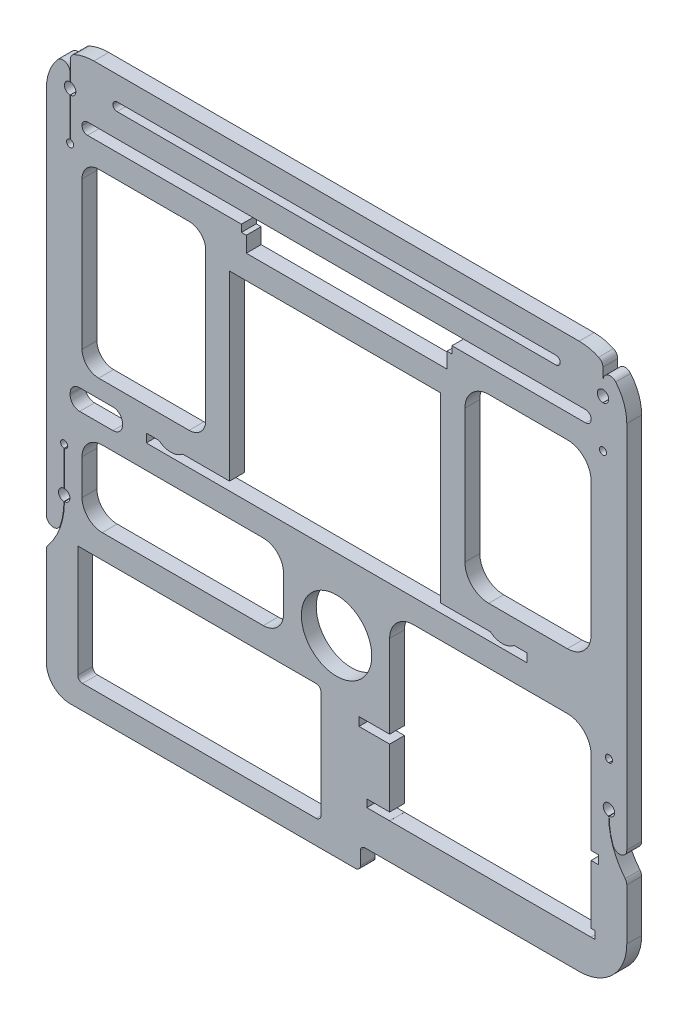
SolidWorks part; units mm, degrees
ref_plane "Front Plane" through (0, 0, 0) normal (0, 0, 1) x (1, 0, 0)
ref_plane "Top Plane" through (0, 0, 0) normal (0, 1, 0) x (1, 0, 0)
ref_plane "Right Plane" through (0, 0, 0) normal (1, 0, 0) x (0, 0, -1)
sketch "Sketch1" plane through (0, 0, 0) normal (0, 0, 1) x (1, 0, 0)
  line L0 (63.9883, 61.406) -> (63.9883, 57.596) construction
  line L1 (11.1776, 3.1158) -> (73.1542, 3.1158)
  line L2 (11.1776, 3.1158) -> (11.1776, 61.406)
  line L3 (11.1776, 61.406) -> (73.1542, 61.406)
  line L4 (73.1542, 3.1158) -> (73.1542, 61.406)
  line L5 (69.3442, 57.596) -> (14.9876, 57.596)
  line L6 (69.3442, 57.596) -> (69.3442, 6.9258)
  line L7 (69.3442, 6.9258) -> (14.9876, 6.9258)
  line L8 (14.9876, 57.596) -> (14.9876, 6.9258)
  line L9 (63.9883, 59.501) -> (18.0707, 59.501) construction
  line L10 (14.9876, 39.3805) -> (11.1776, 39.3805) construction
  line L11 (13.0826, 39.3805) -> (13.0826, 23.9527) construction
  line L12 (13.5248, 6.9258) -> (13.5248, 3.1158) construction
  line L13 (13.5248, 5.0208) -> (21.1598, 5.0208) construction
  line L14 (73.1542, 38.1916) -> (69.3442, 38.1916) construction
  line L15 (71.2492, 38.1916) -> (71.2492, 22.3321) construction
  line L16 (55.7422, 59.501) -> (30.5962, 59.501) construction
  line L19 (42.3087, 5.0208) -> (41.7626, 5.0208) construction
  line L21 (69.3442, 27.6227) -> (69.3442, 52.516) construction
  line L22 (14.9876, 47.563) -> (14.9876, 27.6227) construction
  dimension "D1" = 3.81
  dimension "D2" = 3.81
extrude "Boss-Extrude1" add sketch "Sketch1" along normal blind 1.5875
sketch "Sketch2" plane through (0, 0, 0) normal (0, 0, -1) x (-1, 0, 0)
  line L0 (-69.3442, 6.9258) -> (-69.3442, 57.596) construction
  line L1 (-69.3442, 28.8799) -> (-14.9876, 28.8799)
  line L2 (-69.3442, 28.8799) -> (-69.3442, 26.3399)
  line L3 (-69.3442, 26.3399) -> (-14.9876, 26.3399)
  line L4 (-14.9876, 28.8799) -> (-14.9876, 26.3399)
  line L5 (-14.9876, 57.596) -> (-14.9876, 6.9258) construction
  line L7 (-53.9642, 53.4304) -> (-53.9642, 51.7667)
  line L8 (-32.5266, 53.4304) -> (-32.0059, 53.4304)
  line L9 (-32.5266, 51.7667) -> (-53.9642, 51.7667) construction
  line L10 (-32.5266, 51.7667) -> (-32.5266, 53.4304) construction
  line L11 (-69.3442, 54.1924) -> (-54.4849, 54.1924)
  line L12 (-69.3442, 54.1924) -> (-69.3442, 51.6524)
  line L13 (-69.3442, 51.6524) -> (-55.8692, 51.6524)
  line L14 (-14.9876, 54.1924) -> (-14.9876, 51.6524)
  line L15 (-69.3442, 57.596) -> (-14.9876, 57.596)
  line L16 (-69.3442, 57.596) -> (-69.3442, 55.4243)
  line L17 (-69.3442, 55.4243) -> (-14.9876, 55.4243)
  line L18 (-14.9876, 57.596) -> (-14.9876, 55.4243)
  line L19 (-69.3442, 57.596) -> (-14.9876, 57.596) construction
  line L20 (-54.4849, 54.1924) -> (-54.4849, 53.4304)
  line L21 (-62.3462, 55.4243) -> (-23.9922, 55.4243) construction
  line L22 (-54.4849, 53.4304) -> (-53.9642, 53.4304)
  line L23 (-32.5266, 51.7667) -> (-53.9642, 51.7667)
  line L24 (-32.5266, 51.7667) -> (-32.5266, 53.4304)
  line L25 (-55.8692, 51.6524) -> (-55.8692, 49.2267)
  line L26 (-55.8692, 49.2267) -> (-30.6216, 49.2267)
  line L27 (-30.6216, 49.2267) -> (-30.6216, 51.6524)
  line L28 (-30.6216, 51.6524) -> (-14.9876, 51.6524)
  line L29 (-32.0059, 53.4304) -> (-32.0059, 54.1924)
  line L30 (-62.3462, 54.1924) -> (-23.9922, 54.1924) construction
  line L31 (-62.4859, 28.8799) -> (-21.8459, 28.8799) construction
  line L32 (-54.4849, 53.4304) -> (-54.4849, 54.1924) construction
  line L33 (-32.0059, 53.4304) -> (-54.4849, 53.4304) construction
  line L34 (-32.0059, 54.1924) -> (-14.9876, 54.1924)
  line L36 (-32.0059, 53.4304) -> (-32.0059, 54.1924) construction
  line L37 (-32.5266, 51.7667) -> (-32.5266, 53.4304) construction
  dimension "D1" = 2.54
  dimension "D2" = 1.905
  dimension "D3" = 2.54
  dimension "D4" = 1.905
  dimension "D5" = 2.54
extrude "Boss-Extrude2" add sketch "Sketch2" against normal up to surface (1.5875 mm away) up to face at (42.1659, 32.2609, 1.5875)
sketch "Sketch3" plane through (0, 0, 0) normal (0, 0, -1) x (-1, 0, 0)
  line L1 (-51.983, 32.3343) -> (-51.983, 29.7943) construction
  line L2 (-53.253, 29.7943) -> (-69.3442, 29.7943)
  line L3 (-69.3442, 28.8799) -> (-69.3442, 51.6524) construction
  line L4 (-69.3442, 29.7943) -> (-69.3442, 32.3343)
  line L5 (-69.3442, 32.3343) -> (-55.8692, 32.3343)
  line L7 (-53.253, 29.7943) -> (-53.253, 49.2267)
  line L8 (-55.8692, 49.2267) -> (-30.6216, 49.2267) construction
  line L9 (-53.253, 49.2267) -> (-55.8692, 49.2267)
  line L10 (-55.8692, 49.2267) -> (-55.8692, 32.3343)
  line L12 (-62.4859, 29.7943) -> (-21.8459, 29.7943) construction
  line L13 (-30.7359, 29.7943) -> (-14.9876, 29.7943)
  line L14 (-14.9876, 51.6524) -> (-14.9876, 28.8799) construction
  line L15 (-14.9876, 29.7943) -> (-14.9876, 32.3343)
  line L16 (-14.9876, 32.3343) -> (-28.1959, 32.3343)
  line L17 (-28.1959, 32.3343) -> (-28.1959, 51.6524)
  line L18 (-30.6216, 51.6524) -> (-14.9876, 51.6524) construction
  line L19 (-28.1959, 51.6524) -> (-30.7359, 51.6524)
  line L20 (-30.7359, 51.6524) -> (-30.7359, 29.7943)
  line L21 (-32.0059, 32.3343) -> (-32.0059, 29.7943) construction
  line L22 (-55.8692, 51.6524) -> (-55.8692, 49.2267) construction
  line M22 (-69.3442, 28.8799) -> (-69.3442, 51.6524)
  line M25 (-55.8692, 49.2267) -> (-30.6216, 49.2267)
  line M27 (-30.6216, 51.6524) -> (-14.9876, 51.6524)
  line M28 (-14.9876, 51.6524) -> (-14.9876, 28.8799)
  dimension "D1" = 2.54
  dimension "D3" = 2.54
  dimension "D4" = 2.54
  dimension "D5" = 1.27
  dimension "D6" = 1.27
extrude "Boss-Extrude3" add sketch "Sketch3" against normal up to surface (1.5875 mm away) contours L10 L5 L2 L7 M25 M22 | L20 L13 L16 L17 M27 M28 region at (30.4665, 50.4396, 0) region at (61.2986, 30.0466, 0) up to face at (42.8855, 53.7395, 1.5875)
sketch "Sketch4" plane through (0, 0, 0) normal (0, 0, -1) x (-1, 0, 0)
  line L0 (-69.3442, 26.3399) -> (-14.9876, 26.3399) construction
  line L1 (-47.8301, 26.3399) -> (-36.5017, 26.3399)
  line L2 (-47.8301, 26.3399) -> (-47.8301, 6.9258)
  line L3 (-47.8301, 6.9258) -> (-36.5017, 6.9258)
  line L4 (-36.5017, 26.3399) -> (-36.5017, 6.9258)
  line L5 (-14.9876, 6.9258) -> (-69.3442, 6.9258) construction
  line L6 (-45.9251, 21.2246) -> (-47.8301, 21.2246) construction
  line L7 (-38.4067, 21.2246) -> (-36.5017, 21.2246) construction
  circle A0 centre (-42.1659, 21.2246) radius 3.7592 construction
  dimension "D1" = 1.905
extrude "Boss-Extrude4" add sketch "Sketch4" against normal up to surface (1.5875 mm away) up to face at (21.5917, 41.9934, 1.5875)
sketch "Sketch5" plane through (0, 0, 0) normal (0, 0, -1) x (-1, 0, 0)
  line L0 (-14.5338, 15.7015) -> (-40.4926, 15.7015) construction
  line L3 (-40.4926, 3.2428) -> (-40.4926, 15.7015) construction
  line L4 (-14.5338, 3.2428) -> (-40.4926, 3.2428) construction
  line L5 (-14.5338, 3.2428) -> (-14.5338, 15.7015) construction
  line L6 (-14.5338, 15.7015) -> (-40.4926, 15.7015)
  line L7 (-40.4926, 3.2428) -> (-40.4926, 15.7015)
  line L8 (-14.5338, 3.2428) -> (-40.4926, 3.2428)
  line L9 (-14.5338, 3.2428) -> (-14.5338, 15.7015)
  circle A0 centre (-42.1659, 21.2246) radius 3.7592 construction
  circle A1 centre (-42.1659, 21.2246) radius 3.7592
extrude "Cut-Extrude1" cut sketch "Sketch5" against normal up to surface (1.5875 mm away) up to face at (58.5871, 16.6329, 1.5875)
sketch "Sketch8" plane through (0, 0, 0) normal (0, 0, -1) x (-1, 0, 0)
  line L1 (-36.5017, 15.7015) -> (-14.9876, 15.7015)
  line L2 (-36.5017, 15.7015) -> (-36.5017, 18.2415)
  line L3 (-36.5017, 18.2415) -> (-14.9876, 18.2415)
  line L4 (-14.9876, 15.7015) -> (-14.9876, 18.2415)
  line L5 (-14.9876, 26.3399) -> (-14.9876, 15.7015) construction
  dimension "D1" = 2.54
extrude "Boss-Extrude5" add sketch "Sketch8" against normal up to surface (1.5875 mm away) up to face at (38.4067, 21.2246, 1.5875)
fillet "Fillet1" radius 5.08 3 edges at (73.1542, 3.1158, 0.7937) (11.1776, 61.406, 0.7937) (73.1542, 61.406, 0.7937)
fillet "Fillet2" radius 2.54 4 edges at (69.3442, 51.6524, 0.7937) (55.8692, 32.3343, 0.7937) (69.3442, 32.3343, 0.7937) (55.8692, 51.6524, 0.7937)
fillet "Fillet3" radius 1.778 4 edges at (14.9876, 32.3343, 0.7937) (28.1959, 32.3343, 0.7937) (14.9876, 51.6524, 0.7937) (28.1959, 51.6524, 0.7937)
fillet "Fillet4" radius 0.5842 4 edges at (14.9876, 55.4243, 0.7937) (69.3442, 55.4243, 0.7937) (69.3442, 54.1924, 0.7937) (14.9876, 54.1924, 0.7937)
fillet "Fillet8" radius 2.159 4 edges at (36.5017, 18.2415, 0.7937) (36.5017, 26.3399, 0.7937) (14.9876, 26.3399, 0.7937) (14.9876, 18.2415, 0.7937)
sketch "Sketch6" plane through (0, 0, 0) normal (0, 0, -1) x (-1, 0, 0)
  circle A0 centre (-71.2492, 19.6852) radius 0.6096 construction
  circle A1 centre (-71.2492, 19.6852) radius 0.6096
  circle A4 centre (-70.6142, 57.596) radius 0.6096 construction
  circle A5 centre (-70.6142, 57.596) radius 0.6096
  circle A6 centre (-13.0826, 19.6852) radius 0.6096 construction
  circle A7 centre (-13.0826, 19.6852) radius 0.6096
  circle A10 centre (-13.7176, 57.596) radius 0.6096 construction
  circle A11 centre (-13.7176, 57.596) radius 0.6096
extrude "Cut-Extrude2" cut sketch "Sketch6" against normal up to surface (1.5875 mm away) up to face at (27.5132, 9.4722, 1.5875)
sketch "Sketch7" plane through (0, 0, 0) normal (0, 0, -1) x (-1, 0, 0)
  line L0 (-44.5566, 14.9395) -> (-70.1344, 14.9395) construction
  line L1 (-70.1344, 14.9395) -> (-70.1344, 14.0251) construction
  line L2 (-70.1344, 14.0251) -> (-44.5566, 14.0251) construction
  line L3 (-44.5566, 14.0251) -> (-44.5566, 14.9395) construction
  line L4 (-45.3906, 7.7431) -> (-69.7746, 7.7431) construction
  line L5 (-69.7746, 7.7431) -> (-69.7746, 6.9303) construction
  line L6 (-69.7746, 6.9303) -> (-45.3906, 6.9303) construction
  line L7 (-45.3906, 6.9303) -> (-45.3906, 7.7431) construction
  line L8 (-44.5566, 14.9395) -> (-70.1344, 14.9395)
  line L9 (-70.1344, 14.9395) -> (-70.1344, 14.0251)
  line L10 (-70.1344, 14.0251) -> (-44.5566, 14.0251)
  line L11 (-44.5566, 14.0251) -> (-44.5566, 14.9395)
  line L12 (-45.3906, 7.7431) -> (-69.7746, 7.7431)
  line L13 (-69.7746, 7.7431) -> (-69.7746, 6.9303)
  line L14 (-69.7746, 6.9303) -> (-45.3906, 6.9303)
  line L15 (-45.3906, 6.9303) -> (-45.3906, 7.7431)
  line L20 (-67.1076, 7.7431) -> (-48.0576, 7.7431)
  line L21 (-48.0576, 7.7431) -> (-48.0576, 9.6227)
  line L22 (-48.0576, 9.6227) -> (-67.1076, 9.6227)
  line L23 (-67.1076, 9.6227) -> (-67.1076, 7.7431)
  line L24 (-67.1076, 7.7431) -> (-48.0576, 7.7431)
  line L25 (-48.0576, 7.7431) -> (-48.0576, 9.6227)
  line L26 (-48.0576, 9.6227) -> (-67.1076, 9.6227)
  line L27 (-67.1076, 9.6227) -> (-67.1076, 7.7431)
  dimension "D1" = 0
extrude "Cut-Extrude3" cut sketch "Sketch7" against normal up to surface (1.5875 mm away) contours L14 L15 L12 L13 | L26 L27 L12 L25 | L10 L11 L8 L9 region at (57.3455, 14.4823, 0) region at (57.5826, 7.3367, 0) region at (57.5826, 8.6829, 0) up to face at (13.108, 57.596, 1.5875)
fillet "Fillet6" radius 0.508 3 edges at (40.4926, 15.7015, 0.7937) (40.4926, 3.2428, 0.7937) (14.5338, 3.2428, 0.7937)
sketch "Sketch9" plane through (0, 0, 1.5875) normal (0, 0, 1) x (1, 0, 0)
  line L0 (68.0742, 61.406) -> (16.2576, 61.406) construction
  line L1 (18.2896, 58.866) -> (66.0422, 58.866)
  line L2 (18.2896, 58.866) -> (18.2896, 57.9643)
  line L3 (18.2896, 57.9643) -> (66.0422, 57.9643)
  line L8 (66.0422, 58.866) -> (66.0422, 57.9643)
  line L9 (15.5718, 55.4243) -> (68.76, 55.4243) construction
  line L10 (11.1776, 56.326) -> (11.1776, 59.3208) construction
  line L11 (18.2896, 58.866) -> (11.1776, 58.866) construction
  line L13 (66.0422, 58.866) -> (73.1542, 58.866) construction
  line L14 (73.1542, 56.326) -> (73.1542, 56.8419) construction
  dimension "D1" = 2.54
  dimension "D2" = 2.54
  dimension "D3" = 7.112
extrude "Cut-Extrude4" cut sketch "Sketch9" against normal up to surface (1.5875 mm away) up to face at (58.1379, 12.0542, 0)
fillet "Fillet7" radius 0.4318 4 edges at (18.2896, 57.9643, 0.7937) (18.2896, 58.866, 0.7937) (66.0422, 57.9643, 0.7937) (66.0422, 58.866, 0.7937)
fillet "Fillet9" radius 2.54 2 edges at (69.3442, 26.3399, 0.7937) (47.8301, 26.3399, 0.7937)
sketch "Sketch10" plane through (0, 0, 1.5875) normal (0, 0, 1) x (1, 0, 0)
  line L0 (42.1659, 24.9838) -> (42.1659, -13.4858) construction
  line L1 (11.1776, 3.1158) -> (44.7059, 3.1158)
  line L2 (11.1776, 3.1158) -> (11.1776, 0.7028)
  line L3 (11.1776, 0.7028) -> (44.7059, 0.7028)
  line L4 (44.7059, 3.1158) -> (44.7059, 0.7028)
  line L5 (15.0418, 3.2428) -> (39.9846, 3.2428) construction
  circle A0 centre (42.1659, 21.2246) radius 3.7592 construction
  dimension "D1" = 2.54
  dimension "D2" = 2.54
extrude "Boss-Extrude6" add sketch "Sketch10" against normal up to surface (1.5875 mm away) up to face at (42.1659, 58.4152, 0)
fillet "Fillet10" radius 2.54 1 edges at (11.1776, 0.7028, 0.7937)
fillet "Fillet11" radius 0.508 2 edges at (44.7059, 3.1158, 0.7937) (44.7059, 0.7028, 0.7937)
sketch "Sketch11" plane through (0, 0, 1.5875) normal (0, 0, 1) x (1, 0, 0)
  line L0 (13.7049, 59.0933) -> (13.7049, 58.2055) construction
  line L1 (13.7049, 56.9866) -> (13.7049, 52.8968) construction
  line L2 (13.7303, 52.8968) -> (13.7303, 56.9866) construction
  line L3 (13.7303, 58.2055) -> (13.7303, 60.2667) construction
  line L4 (70.6015, 58.2055) -> (70.6015, 60.2667) construction
  line L5 (70.6269, 56.9866) -> (70.6269, 52.8968) construction
  line L6 (70.6015, 52.8968) -> (70.6015, 56.9866) construction
  line L7 (71.2619, 24.0038) -> (71.2619, 20.2947) construction
  line L8 (71.2365, 24.0038) -> (71.2365, 20.2947) construction
  line L9 (13.0953, 24.0038) -> (13.0953, 20.2947) construction
  line L10 (13.0699, 24.0038) -> (13.0699, 20.2947) construction
  line L11 (13.7049, 59.0933) -> (13.7049, 58.2055)
  line L12 (13.7049, 56.9866) -> (13.7049, 52.8968)
  line L13 (13.7303, 52.8968) -> (13.7303, 56.9866)
  line L14 (13.7303, 58.2055) -> (13.7303, 60.2667)
  line L15 (70.6015, 58.2055) -> (70.6015, 60.2667)
  line L16 (70.6269, 56.9866) -> (70.6269, 52.8968)
  line L17 (70.6015, 52.8968) -> (70.6015, 56.9866)
  line L18 (71.2619, 24.0038) -> (71.2619, 20.2947)
  line L19 (71.2365, 24.0038) -> (71.2365, 20.2947)
  line L20 (13.0953, 24.0038) -> (13.0953, 20.2947)
  line L21 (13.0699, 24.0038) -> (13.0699, 20.2947)
  line L22 (73.1542, 8.1958) -> (73.1542, 56.326) construction
  line L23 (11.1776, 56.326) -> (11.1776, 3.2428) construction
  line L24 (73.1542, 13.6774) -> (73.1542, 16.8829)
  line L25 (11.1776, 16.8829) -> (11.1776, 13.6774)
  line L26 (70.6269, 59.0933) -> (70.6269, 58.2055) construction
  line L27 (70.6269, 59.0933) -> (70.6269, 58.2055)
  arc A0 (13.7049, 59.0933) -> (12.3579, 59.5817) centre (12.9429, 59.0933) ccw construction
  arc A1 (13.7049, 52.8968) -> (13.7303, 52.8968) centre (13.7176, 52.516) ccw construction
  arc A2 (14.1807, 60.9621) -> (13.7303, 60.2667) centre (14.4923, 60.2667) ccw construction
  arc A3 (70.6015, 60.2667) -> (70.151, 60.9621) centre (69.8395, 60.2667) ccw construction
  arc A4 (71.9738, 59.5817) -> (70.6269, 59.0933) centre (71.3889, 59.0933) ccw construction
  arc A5 (70.6015, 52.8968) -> (70.6269, 52.8968) centre (70.6142, 52.516) ccw construction
  arc A6 (71.2619, 24.0038) -> (71.2365, 24.0038) centre (71.2492, 24.3846) ccw construction
  arc A7 (71.2746, 19.0762) -> (71.6692, 16.6421) centre (78.975, 19.0756) ccw construction
  arc A8 (71.6692, 16.6421) -> (73.1542, 16.8829) centre (72.3922, 16.8829) ccw construction
  arc A9 (71.2238, 19.0762) -> (72.9814, 14.1605) centre (78.975, 19.0756) ccw construction
  arc A10 (73.1542, 13.6774) -> (72.9814, 14.1605) centre (72.3922, 13.6774) ccw construction
  arc A11 (13.0953, 24.0038) -> (13.0699, 24.0038) centre (13.0826, 24.3846) ccw construction
  arc A12 (11.3503, 14.1605) -> (13.108, 19.0762) centre (5.3567, 19.0756) ccw construction
  arc A13 (12.6625, 16.6421) -> (13.0572, 19.0762) centre (5.3567, 19.0756) ccw construction
  arc A14 (11.1776, 16.8829) -> (12.6625, 16.6421) centre (11.9396, 16.8829) ccw construction
  arc A15 (11.3503, 14.1605) -> (11.1776, 13.6774) centre (11.9396, 13.6774) ccw construction
  arc A16 (13.7049, 59.0933) -> (12.3579, 59.5817) centre (12.9429, 59.0933) ccw
  arc A17 (13.7049, 52.8968) -> (13.7303, 52.8968) centre (13.7176, 52.516) ccw
  arc A18 (14.1807, 60.9621) -> (13.7303, 60.2667) centre (14.4923, 60.2667) ccw
  arc A19 (70.6015, 60.2667) -> (70.151, 60.9621) centre (69.8395, 60.2667) ccw
  arc A20 (71.9738, 59.5817) -> (70.6269, 59.0933) centre (71.3889, 59.0933) ccw
  arc A21 (70.6015, 52.8968) -> (70.6269, 52.8968) centre (70.6142, 52.516) ccw
  arc A22 (71.2619, 24.0038) -> (71.2365, 24.0038) centre (71.2492, 24.3846) ccw
  arc A23 (71.2746, 19.0762) -> (71.6692, 16.6421) centre (78.975, 19.0756) ccw
  arc A24 (71.6692, 16.6421) -> (73.1542, 16.8829) centre (72.3922, 16.8829) ccw
  arc A25 (71.2238, 19.0762) -> (72.9814, 14.1605) centre (78.975, 19.0756) ccw
  arc A26 (73.1542, 13.6774) -> (72.9814, 14.1605) centre (72.3922, 13.6774) ccw
  arc A27 (13.0953, 24.0038) -> (13.0699, 24.0038) centre (13.0826, 24.3846) ccw
  arc A28 (11.3503, 14.1605) -> (13.108, 19.0762) centre (5.3567, 19.0756) ccw
  arc A29 (12.6625, 16.6421) -> (13.0572, 19.0762) centre (5.3567, 19.0756) ccw
  arc A30 (11.1776, 16.8829) -> (12.6625, 16.6421) centre (11.9396, 16.8829) ccw
  arc A31 (11.3503, 14.1605) -> (11.1776, 13.6774) centre (11.9396, 13.6774) ccw
  arc A32 (16.2576, 61.406) -> (11.1776, 56.326) centre (16.2576, 56.326) ccw construction
  circle A33 centre (13.7176, 57.596) radius 0.6096 construction
  arc A34 (73.1542, 56.326) -> (68.0742, 61.406) centre (68.0742, 56.326) ccw construction
  circle A35 centre (70.6142, 57.596) radius 0.6096 construction
  circle A36 centre (71.2492, 19.6852) radius 0.6096 construction
  circle A37 centre (13.0826, 19.6852) radius 0.6096 construction
  arc A38 (14.1807, 60.9621) -> (12.3579, 59.5817) centre (16.2576, 56.326) ccw
  arc A39 (13.7303, 58.2055) -> (13.7049, 58.2055) centre (13.7176, 57.596) ccw
  arc A40 (71.9738, 59.5817) -> (70.151, 60.9621) centre (68.0742, 56.326) ccw
  arc A41 (70.6015, 56.9866) -> (70.6269, 56.9866) centre (70.6142, 57.596) ccw
  arc A42 (71.2619, 20.2947) -> (71.2365, 20.2947) centre (71.2492, 19.6852) ccw
  arc A43 (13.0572, 19.0762) -> (13.108, 19.0762) centre (13.0826, 19.6852) ccw
  arc A44 (13.0953, 20.2947) -> (13.0699, 20.2947) centre (13.0826, 19.6852) ccw
  arc A45 (13.7049, 56.9866) -> (13.7303, 56.9866) centre (13.7176, 57.596) ccw
  arc A46 (71.2238, 19.0762) -> (71.2746, 19.0762) centre (71.2492, 19.6852) ccw
  arc A47 (70.6015, 56.9866) -> (70.6269, 56.9866) centre (70.6142, 57.596) ccw
  arc A48 (70.6269, 58.2055) -> (70.6015, 58.2055) centre (70.6142, 57.596) ccw
extrude "Cut-Extrude5" cut sketch "Sketch11" against normal through all contours A39 L14 A18 A38 A16 L11 | A45 L12 A17 L13 | A43 A29 A30 L25 A31 A28 | A44 L20 A27 L21 | A46 A25 A26 L24 A24 A23 | A42 L18 A22 L19 | A48 L27 A20 A40 A19 L15 | A41 L17 A21 L16 region at (13.3996, 60.0409, 1.5875) region at (13.7176, 52.9661, 1.5875) region at (70.9321, 60.0409, 1.5875) region at (70.6142, 52.9661, 1.5875) region at (71.2492, 24.0019, 1.5875) region at (13.0826, 24.0019, 1.5875) region at (72.5827, 15.6068, 1.5875) region at (11.749, 15.6068, 1.5875)
sketch "Sketch12" plane through (0, 0, 0) normal (0, 0, -1) x (-1, 0, 0)
  line L0 (-30.7359, 29.7943) -> (-14.9876, 29.7943) construction
  line L1 (-22.8238, 29.7943) -> (-26.1258, 29.7943) construction
  line L2 (-22.8238, 29.7943) -> (-23.2048, 29.7943) construction
  line L3 (-25.7448, 29.7943) -> (-26.1258, 29.7943) construction
  line L4 (-24.4748, 29.3371) -> (-24.4748, 29.7943) construction
  line L5 (-24.4748, 28.8799) -> (-24.4748, 29.7943) construction
  line L6 (-24.4748, 29.3371) -> (-24.4748, 28.8799) construction
  line L7 (-14.9876, 28.8799) -> (-69.3442, 28.8799) construction
  line L8 (-25.7933, 29.7943) -> (-23.2048, 29.7943)
  line L9 (-58.206, 29.7943) -> (-61.508, 29.7943) construction
  line L10 (-58.206, 29.7943) -> (-58.587, 29.7943) construction
  line L11 (-61.127, 29.7943) -> (-61.508, 29.7943) construction
  line L12 (-59.857, 29.3371) -> (-59.857, 28.8799) construction
  line L13 (-61.508, 28.8799) -> (-58.206, 28.8799) construction
  line L14 (-59.857, 29.3371) -> (-59.857, 29.7943) construction
  line L15 (-53.253, 29.7943) -> (-69.3442, 29.7943) construction
  line L16 (-59.857, 28.8799) -> (-59.857, 29.7943) construction
  line L17 (-61.127, 29.7943) -> (-58.587, 29.7943)
  arc A0 (-25.7448, 29.7943) -> (-23.2048, 29.7943) centre (-24.4748, 31.3296) ccw
  arc A1 (-61.127, 29.7943) -> (-58.587, 29.7943) centre (-59.857, 31.3296) ccw
  dimension "D1" = 0.381
extrude "Boss-Extrude7" add sketch "Sketch12" against normal up to surface (1.5875 mm away) contours L8 A0 | L17 A1 region at (24.4748, 29.6095, 0) region at (59.857, 29.6095, 0) up to face at (25.7446, 22.2907, 1.5875)
sketch "Sketch13" plane through (0, 0, 0) normal (0, 0, -1) x (-1, 0, 0)
  line L0 (-62.4859, 29.7943) -> (-62.4859, 28.8799) construction
  line L1 (-62.4859, 29.7943) -> (-62.4859, 28.8799)
  line L2 (-61.127, 29.7943) -> (-69.3442, 29.7943) construction
  line L3 (-69.3442, 28.8799) -> (-69.3442, 29.7943) construction
  line L4 (-14.9876, 28.8799) -> (-69.3442, 28.8799) construction
  line L5 (-62.4859, 29.7943) -> (-69.3442, 29.7943)
  line L6 (-69.3442, 28.8799) -> (-69.3442, 29.7943)
  line L7 (-62.4859, 28.8799) -> (-69.3442, 28.8799)
  line L8 (-21.8459, 29.7943) -> (-21.8459, 28.8799) construction
  line L9 (-21.8459, 29.7943) -> (-21.8459, 28.8799)
  line L10 (-14.9876, 29.7943) -> (-14.9876, 28.8799) construction
  line L11 (-23.2048, 29.7943) -> (-14.9876, 29.7943) construction
  line L12 (-14.9876, 28.8799) -> (-21.8459, 28.8799)
  line L13 (-14.9876, 29.7943) -> (-14.9876, 28.8799)
  line L14 (-21.8459, 29.7943) -> (-14.9876, 29.7943)
  line L15 (-62.4859, 28.8799) -> (-69.3442, 28.8799)
extrude "Boss-Extrude8" add sketch "Sketch13" against normal up to surface (1.5875 mm away) contours L14 L9 L12 L13 | L7 L1 L5 L6 region at (65.915, 29.3371, 0) region at (18.4167, 29.3371, 0) up to face at (25.7446, 22.2907, 1.5875)
sketch "Sketch14" plane through (0, 0, 0) normal (0, 0, -1) x (-1, 0, 0)
  line L0 (-21.8459, 29.3371) -> (-19.3059, 29.3371) construction
  line L1 (-19.3059, 30.4293) -> (-13.7176, 30.4293)
  line L2 (-19.3059, 30.4293) -> (-19.3059, 28.2449)
  line L3 (-19.3059, 28.2449) -> (-13.7176, 28.2449)
  line L4 (-13.7176, 30.4293) -> (-13.7176, 28.2449)
  line L5 (-21.8459, 29.7943) -> (-21.8459, 28.8799) construction
  line L6 (-13.7176, 29.3371) -> (-11.1776, 29.3371) construction
  line L7 (-11.1776, 56.326) -> (-11.1776, 16.8829) construction
  line L8 (-18.0489, 32.3343) -> (-18.0489, 30.4293) construction
  line L9 (-16.7656, 32.3343) -> (-26.4179, 32.3343) construction
  line L11 (-18.0489, 28.2449) -> (-18.0489, 26.3399) construction
  line L12 (-34.3427, 26.3399) -> (-17.1466, 26.3399) construction
  point P4 (-19.3059, 29.3371)
  dimension "D1" = 2.54
  dimension "D2" = 1.905
extrude "Cut-Extrude6" cut sketch "Sketch14" against normal through all
fillet "Fillet12" radius 1.016 4 edges at (13.7176, 30.4293, 0.7938) (13.7176, 28.2449, 0.7937) (19.3059, 28.2449, 0.7938) (19.3059, 30.4293, 0.7938)
